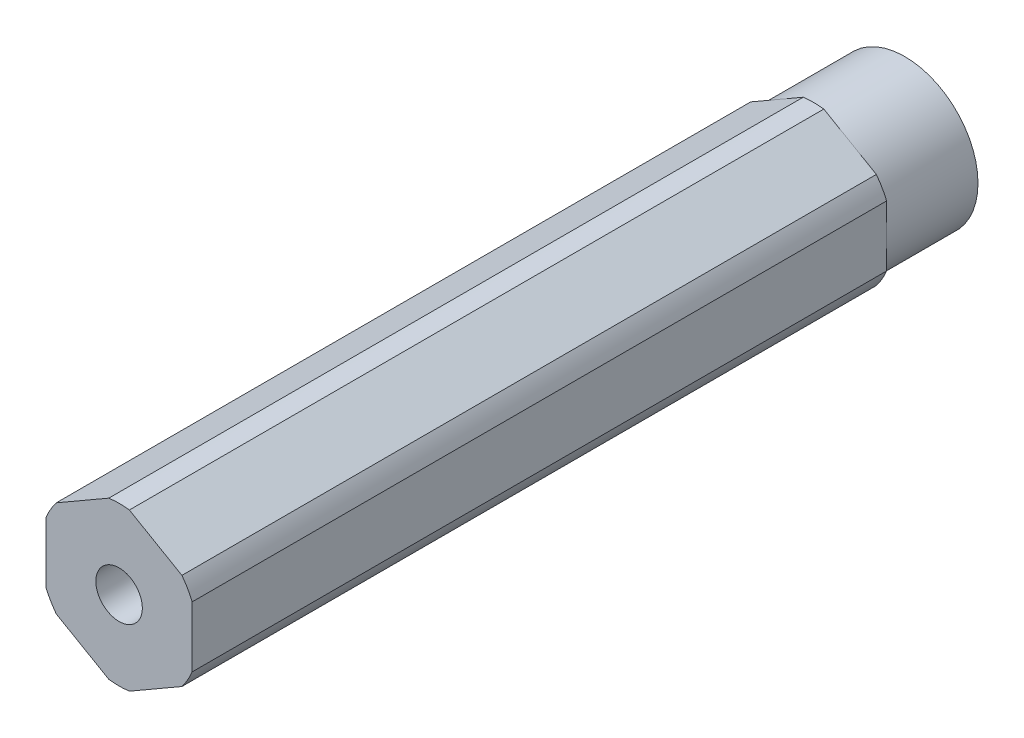
SolidWorks part; units mm, degrees
material "6061-T6 (SS)"
ref_plane "Front Plane" through (0, 0, 0) normal (0, 0, 1) x (1, 0, 0)
ref_plane "Top Plane" through (0, 0, 0) normal (0, 1, 0) x (1, 0, 0)
ref_plane "Right Plane" through (0, 0, 0) normal (1, 0, 0) x (0, 0, -1)
sketch "Sketch1" plane through (0, 0, 0) normal (0, 0, 1) x (1, 0, 0)
  line L0 (0, 7.3323) -> (-0.893, 6.8168) construction
  line L1 (-0.893, 6.8168) -> (-5.457, 4.1818)
  line L2 (-6.35, 2.635) -> (-6.35, -2.635)
  line L3 (-5.457, -4.1818) -> (-0.893, -6.8168)
  line L4 (0.893, -6.8168) -> (5.457, -4.1818)
  line L5 (6.35, -2.635) -> (6.35, 2.635)
  line L6 (5.457, 4.1818) -> (0.893, 6.8168)
  line L7 (0.893, 6.8168) -> (0, 7.3323) construction
  circle A0 centre (0, 0) radius 6.35 construction
  arc A2 (-6.35, -2.635) -> (-5.457, -4.1818) centre (0, 0) ccw
  arc A3 (-5.457, 4.1818) -> (-6.35, 2.635) centre (0, 0) ccw
  arc A4 (0.893, 6.8168) -> (-0.893, 6.8168) centre (0, 0) ccw
  arc A5 (-0.893, -6.8168) -> (0.893, -6.8168) centre (0, 0) ccw
  arc A6 (5.457, -4.1818) -> (6.35, -2.635) centre (0, 0) ccw
  arc A7 (6.35, 2.635) -> (5.457, 4.1818) centre (0, 0) ccw
  dimension "D1" = 12.7
  dimension "D2" = 13.75
extrude "Boss-Extrude1" add sketch "Sketch1" along normal mid plane 68.2625
sketch "Sketch3" plane through (0, 0, 34.1313) normal (0, 0, 1) x (1, 0, 0)
  circle A0 centre (0, 0) radius 2.0193
  dimension "D1" = 4.0386
extrude "Cut-Extrude1" cut sketch "Sketch3" against normal through all
sketch "Sketch8" plane through (0, 0, -34.1313) normal (0, 0, -1) x (-1, 0, 0)
  circle A0 centre (0, 0) radius 6.35
  circle A1 centre (0, 0) radius 6.875
  arc A2 (0.893, 6.8168) -> (-0.893, 6.8168) centre (0, 0) ccw construction
  dimension "D1" = 12.7
extrude "Cut-Extrude3" cut sketch "Sketch8" against normal blind 7.9375
hole_wizard "#10-32 Tapped Hole1" positions "3DSketch1" profile "Sketch9" tap size "#10-32" standard "ANSI Inch"
sketch3d "3DSketch1"
  circle A0 centre (0, 0, 34.1313) radius 2.0193 construction
  circle A1 centre (0, 0, -34.1313) radius 2.0193 construction
  point P0 (0, 0, -34.1313)
  point P2 (0, 0, 34.1313)
  point P7 (0, 0, 36.1506)
  point P8 (0, 0, 0)
  point P11 (0, 0, -32.112)
sketch "Sketch9" plane through (0, 0, -34.1313) normal (1, 0, 0) x (0, 1, 0)
  line L0 (0, 0) -> (0, 13.2428)
  line L1 (0, 13.2428) -> (2.0193, 12.0294)
  line L2 (2.0193, 12.0294) -> (2.0193, 0)
  line L5 (2.0193, 0) -> (0, 0)
  line L10 (0, 13.2428) -> (-2.0193, 12.0294) construction
  line L11 (0, -6.35) -> (0, 107.95) construction
  dimension "Tap Drill Dia." = 4.0386
  dimension "Tap Drill Depth" = 12.0294
  dimension "Drill Angle" = 118
cosmetic thread "Hole Thread1" parameters "D1"=9.652, "D2"=4.826
cosmetic thread "Hole Thread2" parameters "D1"=9.652, "D2"=4.826
